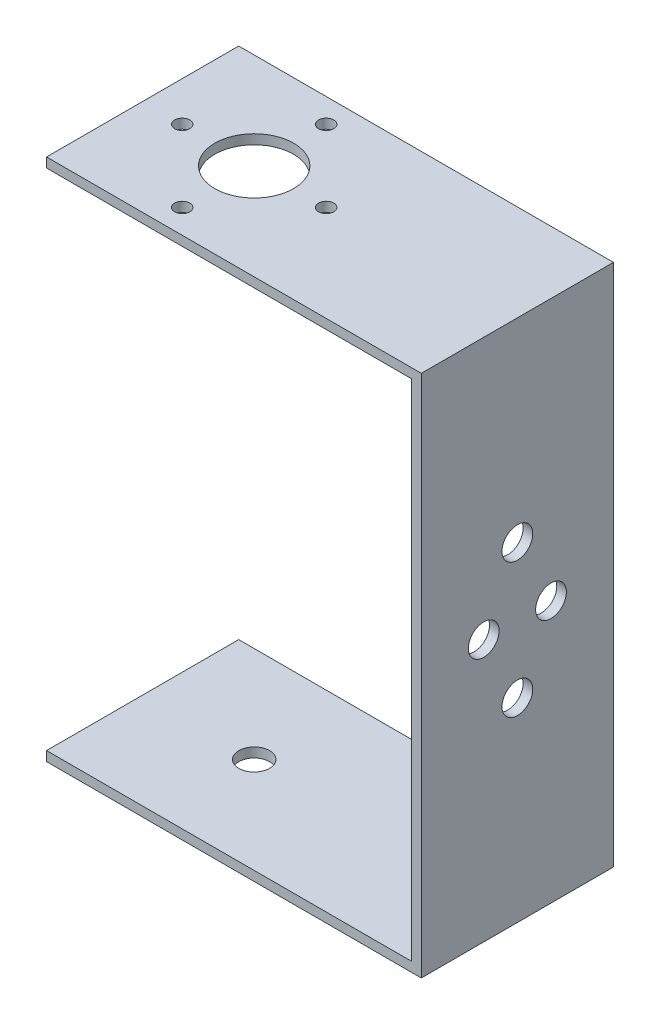
SolidWorks part; units mm, degrees
ref_plane "正面" through (0, 0, 0) normal (0, 0, 1) x (1, 0, 0)
ref_plane "平面" through (0, 0, 0) normal (0, 1, 0) x (1, 0, 0)
ref_plane "右側面" through (0, 0, 0) normal (1, 0, 0) x (0, 0, -1)
sketch "ｽｹｯﾁ1" plane through (0, 0, 0) normal (1, 0, 0) x (0, 0, -1)
  line L1 (0, 0) -> (20, 0)
  line L2 (0, 0) -> (0, 54.5)
  line L3 (0, 54.5) -> (20, 54.5)
  line L4 (20, 0) -> (20, 54.5)
extrude "ﾎﾞｽ - 押し出し1" add sketch "ｽｹｯﾁ1" along normal blind 1
sketch "ｽｹｯﾁ2" plane through (0, 0, 0) normal (-1, 0, 0) x (0, 0, 1)
  line L0 (0, 54.5) -> (0, 0) construction
  line L1 (-20, 54.5) -> (0, 54.5)
  line L2 (-20, 54.5) -> (-20, 53.5)
  line L3 (-20, 53.5) -> (0, 53.5)
  line L4 (0, 54.5) -> (0, 53.5)
extrude "ﾎﾞｽ - 押し出し2" add sketch "ｽｹｯﾁ2" along normal blind 38
sketch "ｽｹｯﾁ3" plane through (0, 0, 0) normal (-1, 0, 0) x (0, 0, 1)
  line L0 (-20, 0) -> (-20, 53.5) construction
  line L1 (0, 0) -> (-20, 0)
  line L2 (0, 0) -> (0, 1)
  line L3 (0, 1) -> (-20, 1)
  line L4 (-20, 0) -> (-20, 1)
extrude "ﾎﾞｽ - 押し出し3" add sketch "ｽｹｯﾁ3" along normal blind 38
sketch "ｽｹｯﾁ4" plane through (0, 54.5, 0) normal (0, 1, 0) x (1, 0, 0)
  circle A0 centre (-26.39, 10) radius 4.1
extrude "ｶｯﾄ - 押し出し1" cut sketch "ｽｹｯﾁ4" against normal blind 1
sketch "ｽｹｯﾁ5" plane through (0, 54.5, 0) normal (0, 1, 0) x (1, 0, 0)
  circle A0 centre (-33.88, 10) radius 0.79
extrude "ｶｯﾄ - 押し出し2" cut sketch "ｽｹｯﾁ5" against normal blind 1
sketch "ｽｹｯﾁ6" plane through (0, 54.5, 0) normal (0, 1, 0) x (1, 0, 0)
  circle A0 centre (-18.9, 10) radius 0.79
extrude "ｶｯﾄ - 押し出し3" cut sketch "ｽｹｯﾁ6" against normal blind 1
sketch "ｽｹｯﾁ7" plane through (0, 54.5, 0) normal (0, 1, 0) x (1, 0, 0)
  circle A0 centre (-26.39, 2.51) radius 0.79
extrude "ｶｯﾄ - 押し出し4" cut sketch "ｽｹｯﾁ7" against normal blind 1
sketch "ｽｹｯﾁ8" plane through (0, 54.5, 0) normal (0, 1, 0) x (1, 0, 0)
  circle A0 centre (-26.39, 17.49) radius 0.79
extrude "ｶｯﾄ - 押し出し5" cut sketch "ｽｹｯﾁ8" against normal blind 1
sketch "ｽｹｯﾁ9" plane through (0, 0, 0) normal (0, -1, 0) x (-1, 0, 0)
  circle A0 centre (26.39, 10) radius 1.6
extrude "ｶｯﾄ - 押し出し6" cut sketch "ｽｹｯﾁ9" against normal blind 1
sketch "ｽｹｯﾁ10" plane through (1, 0, 0) normal (1, 0, 0) x (0, 0, -1)
  circle A0 centre (6.5, 27.25) radius 1.6
extrude "ｶｯﾄ - 押し出し7" cut sketch "ｽｹｯﾁ10" against normal blind 1
sketch "ｽｹｯﾁ11" plane through (1, 0, 0) normal (1, 0, 0) x (0, 0, -1)
  circle A0 centre (10, 34.25) radius 1.6
extrude "ｶｯﾄ - 押し出し8" cut sketch "ｽｹｯﾁ11" against normal blind 1
sketch "ｽｹｯﾁ12" plane through (1, 0, 0) normal (1, 0, 0) x (0, 0, -1)
  circle A0 centre (13.5, 27.25) radius 1.6
extrude "ｶｯﾄ - 押し出し9" cut sketch "ｽｹｯﾁ12" against normal blind 1
sketch "ｽｹｯﾁ13" plane through (1, 0, 0) normal (1, 0, 0) x (0, 0, -1)
  circle A0 centre (10, 20.25) radius 1.6
extrude "ｶｯﾄ - 押し出し10" cut sketch "ｽｹｯﾁ13" against normal blind 1
